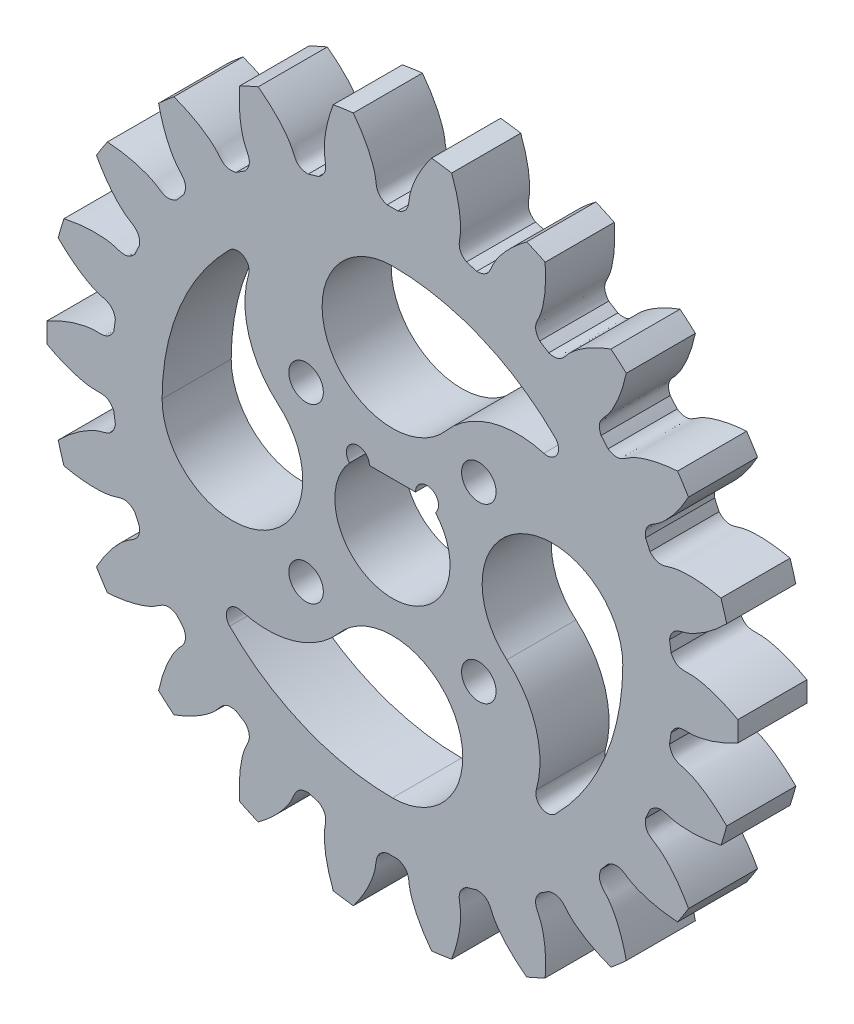
SolidWorks part; units mm, degrees
material "Thornel Mat VMA"
ref_plane "前视基准面" through (0, 0, 0) normal (0, 0, 1) x (1, 0, 0)
ref_plane "上视基准面" through (0, 0, 0) normal (0, 1, 0) x (1, 0, 0)
ref_plane "右视基准面" through (0, 0, 0) normal (1, 0, 0) x (0, 0, -1)
sketch "草图1" plane through (0, 0, 0) normal (0, 0, 1) x (1, 0, 0)
  line L0 (-3, 4) -> (3, 4)
  line L1 (-7.5, 7.5) -> (7.5, -7.5) construction
  line L2 (-7.5, 7.5) -> (7.5, 7.5) construction
  line L3 (-7.5, 7.5) -> (-7.5, -7.5) construction
  line L4 (-7.5, -7.5) -> (7.5, -7.5) construction
  line L5 (7.5, 7.5) -> (7.5, -7.5) construction
  circle A0 centre (0, 0) radius 30
  arc A1 (-3, 4) -> (3, 4) centre (0, 0) ccw
  circle A2 centre (-7.5, 7.5) radius 1.5
  circle A3 centre (7.5, 7.5) radius 1.5
  circle A4 centre (7.5, -7.5) radius 1.5
  circle A5 centre (-7.5, -7.5) radius 1.5
  dimension "D1" = 60
  dimension "D2" = 10
  dimension "D5" = 3
  dimension "D3" = 4
  dimension "D4" = 15
  dimension "D6" = 4
extrude "凸台-拉伸1" add sketch "草图1" along normal blind 6
ref_axis "基准轴1" through (0, 0, 6) along (0, 0, -1)
sketch "草图2" plane through (0, 0, 0) normal (0, 0, 1) x (1, 0, 0)
  line L0 (0, 0) -> (0, 30) construction
  circle A0 centre (0, 0) radius 30 construction
  arc A1 (0.4642, 24.3706) -> (-0.4642, 24.3706) centre (0, 0) ccw
  arc A2 (7.7139, 33.8997) -> (-7.7139, 33.8997) centre (0, 0) ccw
  spline S0 degree 3 poles (0.4642, 24.3706) (1.4704, 24.6905) (1.3709, 25.3794) (1.499, 26.0539) (1.5149, 26.1298) (1.5347, 26.2154) (1.5587, 26.3106) (1.5873, 26.4153) (1.621, 26.5293) (1.66, 26.6525) (1.7049, 26.7847) (1.7558, 26.9256) (1.8133, 27.0752) (1.8776, 27.2331) (1.9492, 27.3993) (2.0284, 27.5734) (2.1155, 27.7551) (2.2109, 27.9444) (2.3148, 28.1408) (2.4277, 28.3442) (2.5498, 28.5542) (2.6815, 28.7705) (2.823, 28.9929) (2.9747, 29.221) (3.1368, 29.4545) (3.3096, 29.6932) (3.4933, 29.9365) (3.6883, 30.1843) (3.8948, 30.4361) (4.1129, 30.6916) (4.343, 30.9504) (4.5852, 31.2121) (4.8398, 31.4764) (5.1069, 31.7429) (5.3868, 32.0111) (5.6796, 32.2807) (5.9855, 32.5512) (6.3046, 32.8222) (6.637, 33.0933) (7.1037, 33.4586) (7.4661, 33.7249) (7.7139, 33.8997) knots 0 0 0 0 0.157021 0.162531 0.168888 0.176093 0.184146 0.193046 0.202794 0.213389 0.224833 0.237123 0.250262 0.264248 0.279082 0.294763 0.311292 0.328669 0.346893 0.365965 0.385884 0.406652 0.428266 0.450729 0.474039 0.498197 0.523202 0.549055 0.575756 0.603304 0.6317 0.660944 0.691035 0.721974 0.75376 0.786395 0.819876 0.854206 0.889383 0.925408 1 1 1 1
  spline S1 degree 3 poles (-0.4642, 24.3706) (-1.4704, 24.6905) (-1.3709, 25.3794) (-1.499, 26.0539) (-1.5149, 26.1298) (-1.5347, 26.2154) (-1.5587, 26.3106) (-1.5873, 26.4153) (-1.621, 26.5293) (-1.66, 26.6525) (-1.7049, 26.7847) (-1.7558, 26.9256) (-1.8133, 27.0752) (-1.8776, 27.2331) (-1.9492, 27.3993) (-2.0284, 27.5734) (-2.1155, 27.7551) (-2.2109, 27.9444) (-2.3148, 28.1408) (-2.4277, 28.3442) (-2.5498, 28.5542) (-2.6815, 28.7705) (-2.823, 28.9929) (-2.9747, 29.221) (-3.1368, 29.4545) (-3.3096, 29.6932) (-3.4933, 29.9365) (-3.6883, 30.1843) (-3.8948, 30.4361) (-4.1129, 30.6916) (-4.343, 30.9504) (-4.5852, 31.2121) (-4.8398, 31.4764) (-5.1069, 31.7429) (-5.3868, 32.0111) (-5.6796, 32.2807) (-5.9855, 32.5512) (-6.3046, 32.8222) (-6.637, 33.0933) (-7.1037, 33.4586) (-7.4661, 33.7249) (-7.7139, 33.8997) knots 0 0 0 0 0.157021 0.162531 0.168888 0.176093 0.184146 0.193046 0.202794 0.213389 0.224833 0.237123 0.250262 0.264248 0.279082 0.294763 0.311292 0.328669 0.346893 0.365965 0.385884 0.406652 0.428266 0.450729 0.474039 0.498197 0.523202 0.549055 0.575756 0.603304 0.6317 0.660944 0.691035 0.721974 0.75376 0.786395 0.819876 0.854206 0.889383 0.925408 1 1 1 1
extrude "切除-拉伸1" cut sketch "草图2" along normal through all
pattern_circular "阵列(圆周)1" count 22 every 16.364 about axis through (0, 0, 6) along (0, 0, -1) of "切除-拉伸1"
sketch "草图3" plane through (0, 0, 6) normal (0, 0, 1) x (1, 0, 0)
  circle A0 centre (-3, 4) radius 1
  circle A1 centre (3, 4) radius 1
  arc A2 (0, 20) -> (4.6463, 9.9329) centre (0, 13.8942) ccw
  circle A3 centre (0, 0) radius 13.8942 construction
  arc A4 (0, 20) -> (14.1304, 14.1539) centre (0, 0) cw
  arc A5 (4.6463, 9.9329) -> (13.1462, 12.4855) centre (10.8741, 4.6234) cw
  arc A7 (14.1304, 14.1539) -> (13.1462, 12.4855) centre (13.4238, 13.4462) cw
  arc A8 (20, 0) -> (9.9329, -4.6463) centre (13.8942, 0) ccw
  arc A9 (9.9329, -4.6463) -> (12.4855, -13.1462) centre (4.6234, -10.8741) cw
  arc A10 (14.1539, -14.1304) -> (12.4855, -13.1462) centre (13.4462, -13.4238) cw
  arc A11 (20, 0) -> (14.1539, -14.1304) centre (0, 0) cw
  arc A12 (0, -20) -> (-4.6463, -9.9329) centre (0, -13.8942) ccw
  arc A13 (-4.6463, -9.9329) -> (-13.1462, -12.4855) centre (-10.8741, -4.6234) cw
  arc A14 (-14.1304, -14.1539) -> (-13.1462, -12.4855) centre (-13.4238, -13.4462) cw
  arc A15 (0, -20) -> (-14.1304, -14.1539) centre (0, 0) cw
  arc A16 (-20, 0) -> (-9.9329, 4.6463) centre (-13.8942, 0) ccw
  arc A17 (-9.9329, 4.6463) -> (-12.4855, 13.1462) centre (-4.6234, 10.8741) cw
  arc A18 (-14.1539, 14.1304) -> (-12.4855, 13.1462) centre (-13.4462, 13.4238) cw
  arc A19 (-20, 0) -> (-14.1539, 14.1304) centre (0, 0) cw
  circle A20 centre (7.5, 7.5) radius 3.75 construction
  dimension "D1" = 2
  dimension "D2" = 20
  dimension "D4" = 1
  dimension "D6" = 7.5
  dimension "D5" = 4
extrude "切除-拉伸2" cut sketch "草图3" against normal through all
